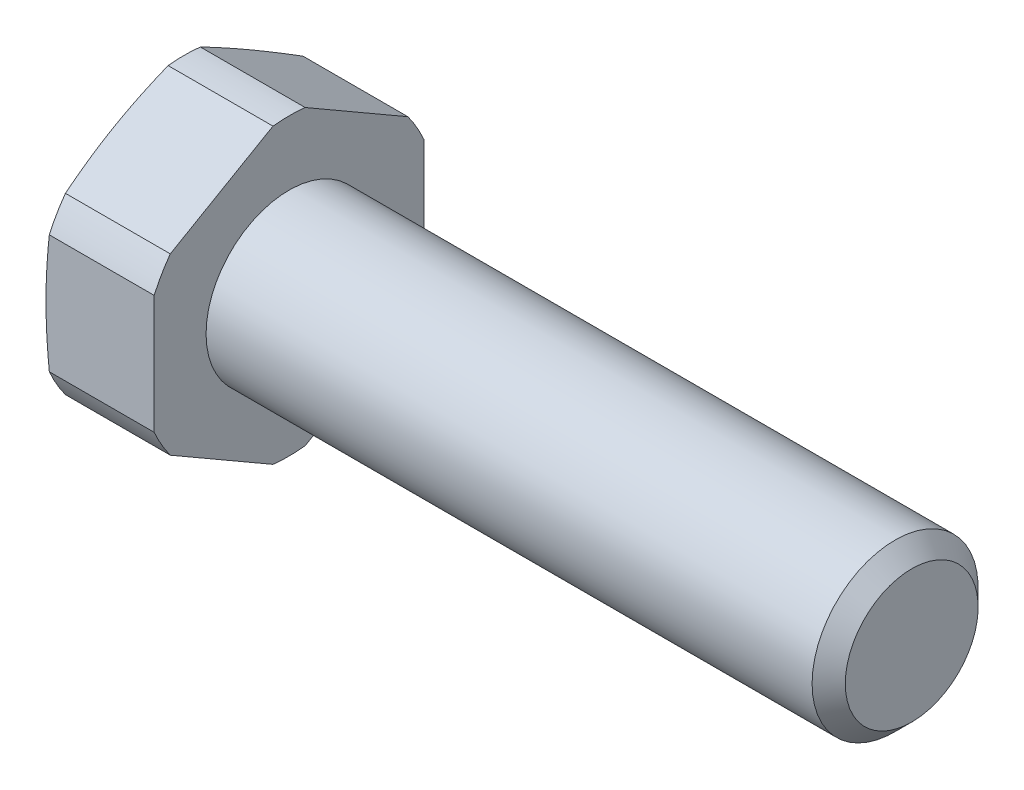
SolidWorks part; units mm, degrees
material "AISI 1020"
ref_plane "Спереди" through (0, 0, 0) normal (0, 0, 1) x (1, 0, 0)
ref_plane "Сверху" through (0, 0, 0) normal (0, 1, 0) x (1, 0, 0)
ref_plane "Справа" through (0, 0, 0) normal (1, 0, 0) x (0, 0, -1)
sketch "Эскиз1" plane through (0, 0, 0) normal (0, 0, 1) x (1, 0, 0)
  line L0 (-1000, 0) -> (49000, 0) construction
  line L1 (-5.3, 0) -> (-5.3, 6.175)
  line L2 (-5.3, 6.175) -> (-5.0521, 7.1)
  line L3 (-5.0521, 7.1) -> (0, 7.1)
  line L4 (0, 7.1) -> (0, 4)
  line L5 (0, 4) -> (29.2, 4)
  line L6 (30, 3.2) -> (30, 0)
  line L7 (30, 4) -> (30.625, 5.0825) construction
  line L8 (30.625, 5.0825) -> (31.25, 4) construction
  line L9 (31.25, 4) -> (30, 4) construction
  line L10 (30.625, 5.0825) -> (30.625, 4) construction
  line L11 (30.625, 5.0825) -> (8.625, 5.0825) construction
  line L12 (29.2, 4) -> (30, 3.2)
  line L13 (30, 4) -> (29.6, 3.6) construction
  line L14 (-5.3, 6.175) -> (-18.3, 6.175) construction
  line L15 (-5.3, 0) -> (30, 0)
  dimension "D1" = 0.8
  dimension "D2" = 15
revolve "Повернуть1" add sketch "Эскиз1" angle 360 about L0
cosmetic thread "Условное изображение резьбы1" parameters "D1"=22, "D2"=5.8349
sketch "Эскиз2" plane through (-5.3, 0, 0) normal (-1, 0, 0) x (0, 0, 1)
  line L1 (0, 7.5056) -> (-6.5, 3.7528)
  line L2 (-6.5, 3.7528) -> (-6.5, -3.7528)
  line L3 (-6.5, -3.7528) -> (0, -7.5056)
  line L4 (0, -7.5056) -> (6.5, -3.7528)
  line L5 (6.5, -3.7528) -> (6.5, 3.7528)
  line L6 (6.5, 3.7528) -> (0, 7.5056)
  circle A0 centre (0, 0) radius 6.5 construction
  dimension "D1" = 13
extrude "Вырез-Вытянуть1" cut sketch "Эскиз2" against normal up to surface (35.3 mm away) flip side to cut up to face at (30, 0, 3.2)
equation "\"D1@Эскиз1\"=\"_d_@Эскиз1\"/10"
equation "\"D@Эскиз1\"=\"S_@Эскиз1\"*0.95"
equation "\"D1@Эскиз2\"=\"S_@Эскиз1\""
equation "\"D1@Условное изображение резьбы1\"=\"b_@Эскиз1\""
equation "\"D2@Условное изображение резьбы1\"=\"_d_@Эскиз1\"-\"dr@Эскиз1\"*2"
